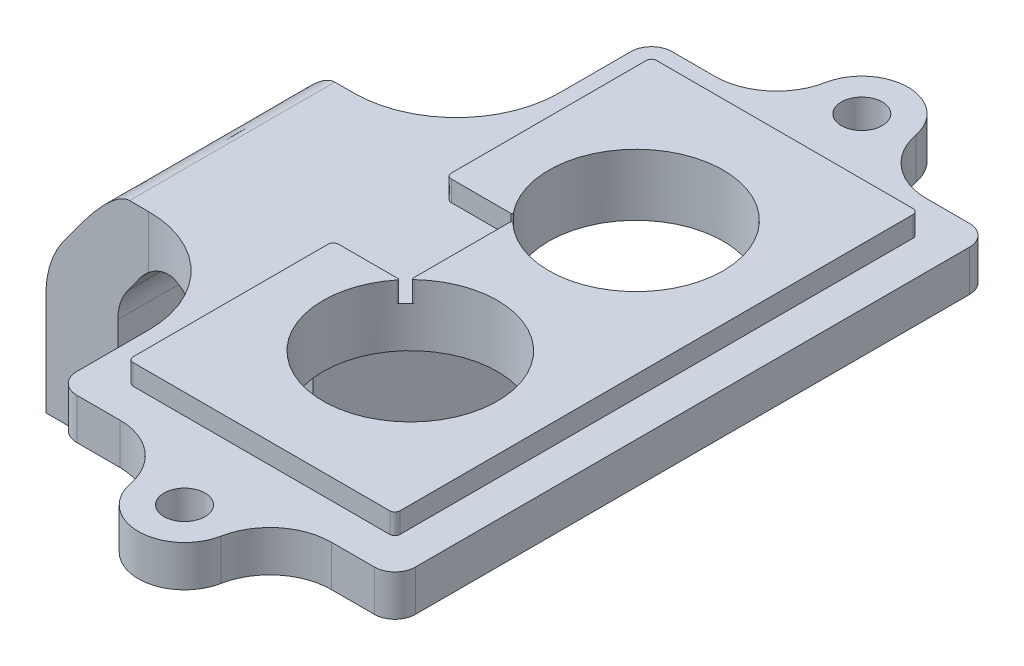
SolidWorks part; units mm, degrees
ref_plane "Plan de face" through (0, 0, 0) normal (0, 0, 1) x (1, 0, 0)
ref_plane "Plan de dessus" through (0, 0, 0) normal (0, 1, 0) x (1, 0, 0)
ref_plane "Plan de droite" through (0, 0, 0) normal (1, 0, 0) x (0, 0, -1)
sketch "Esquisse1" plane through (0, 0, 0) normal (0, 0, 1) x (1, 0, 0)
  line L0 (0, 0) -> (0, 18)
  line L1 (0, 18) -> (15, 18)
  line L2 (15, 18) -> (15, 0)
  line L3 (15, 0) -> (19, 0)
  line L6 (-7, 22) -> (-7, 0)
  line L7 (-7, 0) -> (0, 0)
  line L8 (19, 0) -> (19, 18)
  line L9 (19, 18) -> (46, 18)
  line L10 (46, 18) -> (46, 22)
  line L11 (-7, 22) -> (46, 22)
  dimension "D1" = 7
  dimension "D2" = 4
  dimension "D3" = 27
  dimension "D4" = 4
  dimension "D5" = 15
  dimension "D6" = 4
  dimension "D7" = 18
extrude "Boss.-Extru.1" add sketch "Esquisse1" along normal blind 58 contours L0 L1 L2 L3 L8 L9 L10 L11 L6 L7
sketch "Esquisse16" plane through (0, 22, 0) normal (0, 1, 0) x (1, 0, 0)
  line L112 (17, -3) -> (42, -3)
  line L113 (19.1922, -58) -> (19.1922, -64) construction
  line L114 (39.8078, -58) -> (39.8078, -64) construction
  line L115 (33.9176, -62.8571) -> (25.0824, -62.8571) construction
  line L116 (39.8078, -58) -> (19.1922, -58) construction
  line L117 (42, -3) -> (42, 0)
  line L118 (42, 0) -> (39.8078, 0)
  line L119 (29.5, -3) -> (29.5, 4) construction
  line L120 (19.1922, 0) -> (17, 0)
  line L121 (17, 0) -> (17, -3)
  line L122 (39.8078, 0) -> (19.1922, 0) construction
  line L123 (33.9176, 4.8571) -> (25.0824, 4.8571) construction
  line L124 (39.8078, 0) -> (39.8078, 6) construction
  line L125 (19.1922, 0) -> (19.1922, 6) construction
  line L126 (29.5, -55) -> (29.5, -62) construction
  line L127 (17, -58) -> (17, -55)
  line L128 (19.1922, -58) -> (17, -58)
  line L129 (42, -58) -> (39.8078, -58)
  line L130 (42, -55) -> (42, -58)
  line L131 (17, -55) -> (42, -55)
  line L132 (42, 0) -> (46, 0) construction
  arc A80 (25.0824, 4.8571) -> (33.9176, 4.8571) centre (29.5, 4) cw
  arc A81 (33.9176, 4.8571) -> (39.8078, 0) centre (39.8078, 6) ccw
  arc A82 (25.0824, 4.8571) -> (19.1922, 0) centre (19.1922, 6) cw
  circle A83 centre (29.5, 4) radius 2
  circle A84 centre (29.5, -62) radius 2
  arc A85 (25.0824, -62.8571) -> (19.1922, -58) centre (19.1922, -64) ccw
  arc A86 (33.9176, -62.8571) -> (39.8078, -58) centre (39.8078, -64) cw
  arc A87 (25.0824, -62.8571) -> (33.9176, -62.8571) centre (29.5, -62) ccw
  point P33 (29.5, 0)
  point P59 (29.5, -58)
  dimension "D8" = 25
  dimension "D10" = 6
  dimension "D11" = 4.5
  dimension "D13" = 4
  dimension "D9" = 3
  dimension "D12" = 4
  dimension "D14" = 4
extrude "Boss.-Extru.2" add sketch "Esquisse16" against normal up to surface (4 mm away) up to face at (7.5, 18, 29)
sketch "Esquisse9" plane through (-7, 0, 0) normal (-1, 0, 0) x (0, 0, 1)
  line L0 (58, 22) -> (58, 0) construction
  line L1 (58, 0) -> (0, 0) construction
  line L2 (0, 22) -> (0, 0) construction
  circle A0 centre (33.5, 7) radius 2
  circle A1 centre (24.5, 7) radius 2
  dimension "D1" = 4
  dimension "D4" = 4
  dimension "D2" = 24.5
  dimension "D3" = 7
  dimension "D5" = 24.5
  dimension "D6" = 7
extrude "Enlèv. mat.-Extru.5" cut sketch "Esquisse9" against normal blind 10
sketch "Esquisse14" plane through (0, 22, 0) normal (0, 1, 0) x (1, 0, 0)
  line L0 (46, -58) -> (46, 0) construction
  line L1 (-7, 0) -> (13, 0)
  line L2 (-7, 0) -> (-7, -19)
  line L3 (-7, -19) -> (13, -19)
  line L4 (13, 0) -> (13, -19)
  line L5 (-7, -58) -> (13, -58)
  line L6 (-7, -58) -> (-7, -39)
  line L7 (-7, -39) -> (13, -39)
  line L8 (13, -58) -> (13, -39)
  dimension "D1" = 19
  dimension "D2" = 33
  dimension "D3" = 19
  dimension "D4" = 33
extrude "Enlèv. mat.-Extru.7" cut sketch "Esquisse14" against normal through all
sketch "Esquisse5" plane through (0, 0, 0) normal (0, -1, 0) x (1, 0, 0)
  line L0 (0, 39) -> (0, 19) construction
  line L1 (-1.75, 37.25) -> (-5.25, 37.25)
  line L2 (-1.75, 37.25) -> (-1.75, 29.75)
  line L3 (-1.75, 29.75) -> (-5.25, 29.75)
  line L4 (-5.25, 37.25) -> (-5.25, 29.75)
  line L5 (-1.75, 37.25) -> (-5.25, 29.75) construction
  line L6 (-1.75, 29.75) -> (-5.25, 37.25) construction
  line L7 (-3.5, 0) -> (-3.5, 58) construction
  line L8 (-7, 0) -> (0, 0) construction
  line L9 (-7, 58) -> (0, 58) construction
  line L10 (-5.25, 20.75) -> (-1.75, 20.75)
  line L11 (-5.25, 20.75) -> (-5.25, 28.25)
  line L12 (-5.25, 28.25) -> (-1.75, 28.25)
  line L13 (-1.75, 20.75) -> (-1.75, 28.25)
  line L14 (-5.25, 20.75) -> (-1.75, 28.25) construction
  line L15 (-5.25, 28.25) -> (-1.75, 20.75) construction
  point P0 (-3.5, 33.5)
  point P5 (0, 29)
  point P13 (-3.5, 24.5)
  dimension "D1" = 3.5
  dimension "D2" = 7.5
  dimension "D3" = 7.5
  dimension "D4" = 3.5
  dimension "D5" = 24.5
  dimension "D6" = 24.5
extrude "Enlèv. mat.-Extru.3" cut sketch "Esquisse5" against normal blind 12
fillet "Congé6" radius 2 4 edges at (46, 20, 0) (46, 20, 58) (13, 20, 58) (13, 20, 0)
fillet "Congé11" radius 10 2 edges at (13, 20, 19) (13, 20, 39)
sketch "Esquisse15" plane through (0, 0, 0) normal (0, -1, 0) x (1, 0, 0)
  line L0 (65.6982, 39) -> (65.6982, 19) construction
  line L1 (-7, 19) -> (65.6982, 19)
  line L2 (-7, 19) -> (-7, -31)
  line L3 (-7, -31) -> (65.6982, -31)
  line L4 (65.6982, 19) -> (65.6982, -31)
  line L5 (-7, 39) -> (65.6982, 39)
  line L6 (-7, 39) -> (-7, 89)
  line L7 (-7, 89) -> (65.6982, 89)
  line L8 (65.6982, 39) -> (65.6982, 89)
  dimension "D1" = 50
  dimension "D2" = 50
extrude "Enlèv. mat.-Extru.8" cut sketch "Esquisse15" against normal up to surface (18 mm away) up to face at (32.4877, 18, 29)
sketch "Esquisse17" plane through (0, 22, 0) normal (0, 1, 0) x (1, 0, 0)
  line L0 (46, -29) -> (29.5, -29) construction
  line L1 (46, -56) -> (46, -2) construction
  line L2 (29.5, -29) -> (29.5, -18) construction
  line L3 (29.5, -29) -> (29.5, -40) construction
  circle A0 centre (29.5, -18) radius 8.5
  circle A1 centre (29.5, -40) radius 8.5
  dimension "D4" = 17
  dimension "D5" = 17
  dimension "D1" = 16.5
  dimension "D2" = 11
  dimension "D3" = 11
extrude "Enlèv. mat.-Extru.9" cut sketch "Esquisse17" against normal blind 10
chamfer "Chanfrein1" distance 9 angle 36 1 edges at (-7, 22, 29) first distance on face at (-7, 5, 33.5)
chamfer "Chanfrein2" distance 5 angle 36 1 edges at (0, 18, 29) first distance on face at (0, 7, 35.5)
fillet "Congé14" radius 5 2 edges at (3.6327, 18, 29) (0, 13, 29)
fillet "Congé15" radius 8 1 edges at (-0.4611, 22, 29) second distance 6 first distance on face at (-3.7306, 17.5, 29)
fillet "Congé16" radius 9 1 edges at (-7, 13, 29) first distance on face at (-5.3556, 15.2634, 31.5)
sketch "Esquisse19" plane through (0, 22, 0) normal (0, 1, 0) x (1, 0, 0)
  line L0 (23.5, -24.0208) -> (23.5, -33.9792)
  line L1 (17, -54.5) -> (42, -54.5)
  line L3 (17, -3.5) -> (42, -3.5)
  line L4 (42.5, -54) -> (42.5, -4)
  line L5 (15, -58) -> (19.1922, -58) construction
  line L6 (46, -56) -> (46, -2) construction
  line L7 (39.8078, 0) -> (44, 0) construction
  line L13 (17, -23.5) -> (23.0193, -23.5)
  line L15 (23.0193, -34.5) -> (17, -34.5)
  line L16 (16.5, -23) -> (16.5, -4)
  line L17 (16.5, -35) -> (16.5, -54)
  line L18 (23.0193, -23.5) -> (23.0193, -34.5) construction
  circle A0 centre (29.5, -40) radius 8.5
  circle A1 centre (29.5, -18) radius 8.5
  arc A4 (17, -54.5) -> (16.5, -54) centre (17, -54) cw
  arc A5 (42, -54.5) -> (42.5, -54) centre (42, -54) ccw
  arc A6 (42, -3.5) -> (42.5, -4) centre (42, -4) cw
  arc A7 (16.5, -4) -> (17, -3.5) centre (17, -4) cw
  arc A8 (17, -34.5) -> (16.5, -35) centre (17, -35) ccw
  arc A9 (17, -23.5) -> (16.5, -23) centre (17, -23) cw
  point P10 (20, -29)
  point P11 (42.5, -29)
  point P19 (23.0193, -29)
  point P41 (16.5, -23.5)
  circle M5 centre (29.5, -18) radius 8.5
  circle M6 centre (29.5, -40) radius 8.5
  dimension "D5" = 17
  dimension "D6" = 17
  dimension "D8" = 7
  dimension "D9" = 0.5
  dimension "D2" = 3.5
  dimension "D3" = 3.5
  dimension "D4" = 3.5
  dimension "D7" = 11
  dimension "D10" = 26
extrude "Boss.-Extru.3" add sketch "Esquisse19" along normal blind 2 contours A9 L13 L0 L15 A8 L17 A4 L1 A5 L4 A6 L3 A7 L16 M5 M6 region at (30.4199, 22, 29)
fillet "Congé17" radius 0.1 4 edges at (23.0193, 23, 23.5) (23.5, 23, 33.9792) (23.0193, 23, 34.5) (23.5, 23, 24.0208)
equation "\"D2@Esquisse15\"=\"D1@Esquisse15\""
equation "\"D1@Esquisse17\"=4.5+3+8+1"
